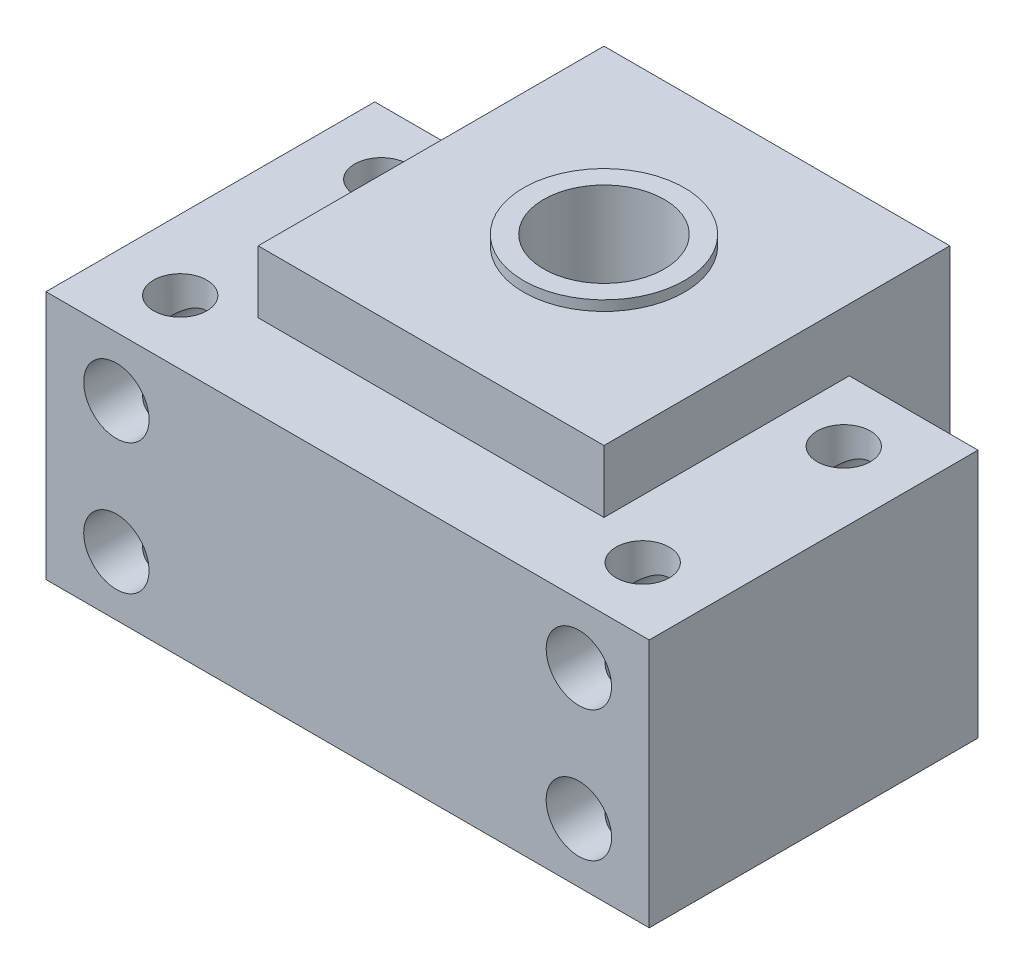
SolidWorks part; units mm, degrees
ref_plane "Front Plane" through (0, 0, 0) normal (0, 0, 1) x (1, 0, 0)
ref_plane "Top Plane" through (0, 0, 0) normal (0, 1, 0) x (1, 0, 0)
ref_plane "Right Plane" through (0, 0, 0) normal (1, 0, 0) x (0, 0, -1)
sketch "Sketch1" plane through (0, 0, 0) normal (0, 1, 0) x (1, 0, 0)
  line L0 (0, 0) -> (0, -9.15) construction
  line L1 (-17.2, -17.2) -> (17.2, -17.2)
  line L2 (-17.2, -17.2) -> (-17.2, 17.2)
  line L3 (-17.2, 17.2) -> (17.2, 17.2)
  line L4 (17.2, -17.2) -> (17.2, 17.2)
  line L5 (-17.2, -17.2) -> (17.2, 17.2) construction
  line L6 (-17.2, 17.2) -> (17.2, -17.2) construction
  line L7 (-30, 7.2) -> (30, 7.2)
  line L8 (-30, 7.2) -> (-30, -25.5)
  line L9 (-30, -25.5) -> (30, -25.5)
  line L10 (30, 7.2) -> (30, -25.5)
  line L11 (-30, 7.2) -> (30, -25.5) construction
  line L12 (-30, -25.5) -> (30, 7.2) construction
  circle A0 centre (0, 0) radius 6
  point P0 (0, 0)
  point P6 (0, -9.15)
  dimension "D6" = 12
  dimension "D1" = 60
  dimension "D2" = 32.7
  dimension "D3" = 42.7
  dimension "D4" = 34.4
  dimension "D5" = 34.4
extrude "Boss-Extrude1" add sketch "Sketch1" along normal blind 24.8 contours L10 L7 L4 L1 L2 L8 L9 | L7 L2 L1 L4 A0 | L2 L7 L4 L3 region at (-16.7783, 0, 5) region at (0, 0, 17.8833) region at (0, 0, -12.2)
extrude "Boss-Extrude2" add sketch "Sketch1<3>" along normal blind 31 contours L2 L7 L4 L3 | L7 L2 L1 L4 A0 region at (-16.7783, 0, 5) region at (0, 0, -12.2)
sketch "Sketch1<3>" plane through (0, 0, 0) normal (0, 1, 0) x (1, 0, 0) same geometry as "Sketch1"
sketch "Sketch3" plane through (0, 0, 25.5) normal (0, 0, 1) x (1, 0, 0)
  line L0 (0, 0) -> (0, 24.8) construction
  line L1 (-30, 0) -> (30, 0) construction
  line L2 (-30, 24.8) -> (30, 24.8) construction
  line L3 (0, 12.4) -> (-23, 12.4) construction
  line L4 (-23, 5.9) -> (23, 5.9) construction
  line L5 (-23, 5.9) -> (-23, 18.9) construction
  line L6 (-23, 18.9) -> (23, 18.9) construction
  line L7 (23, 5.9) -> (23, 18.9) construction
  line L8 (-23, 5.9) -> (23, 18.9) construction
  line L9 (-23, 18.9) -> (23, 5.9) construction
  circle A0 centre (-23, 18.9) radius 3.25
  circle A1 centre (-23, 5.9) radius 3.25
  circle A2 centre (23, 5.9) radius 3.25
  circle A3 centre (23, 18.9) radius 3.25
  point P6 (0, 12.4)
  dimension "D3" = 6.5
  dimension "D1" = 13
  dimension "D2" = 46
extrude "Cut-Extrude1" cut sketch "Sketch3" against normal through all
sketch "Sketch4" plane through (0, 0, 0) normal (0, -1, 0) x (1, 0, 0)
  line L0 (-30, 9.15) -> (30, 9.15) construction
  line L1 (-30, -7.2) -> (-30, 25.5) construction
  line L2 (30, -7.2) -> (30, 25.5) construction
  line L3 (0, 9.15) -> (0, 19.15) construction
  line L4 (-23, -0.85) -> (23, -0.85) construction
  line L5 (-23, -0.85) -> (-23, 19.15) construction
  line L6 (-23, 19.15) -> (23, 19.15) construction
  line L7 (23, -0.85) -> (23, 19.15) construction
  line L8 (-23, -0.85) -> (23, 19.15) construction
  line L9 (-23, 19.15) -> (23, -0.85) construction
  circle A0 centre (-23, 19.15) radius 2.65
  circle A1 centre (-23, -0.85) radius 2.65
  circle A2 centre (23, -0.85) radius 2.65
  circle A3 centre (23, 19.15) radius 2.65
  point P6 (0, 9.15)
  dimension "D3" = 5.3
  dimension "D1" = 20
  dimension "D2" = 46
extrude "Cut-Extrude2" cut sketch "Sketch4" against normal through all
sketch "Sketch5" plane through (0, 31, 0) normal (0, 1, 0) x (1, 0, 0)
  circle A0 centre (0, 0) radius 8
  circle A1 centre (0, 0) radius 6
  dimension "D1" = 16
extrude "Boss-Extrude3" add sketch "Sketch5" along normal blind 1
